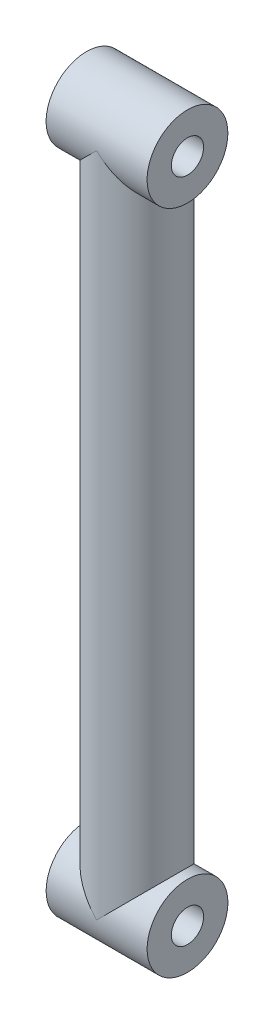
SolidWorks part; units mm, degrees
ref_plane "Front Plane" through (0, 0, 0) normal (0, 0, 1) x (1, 0, 0)
ref_plane "Top Plane" through (0, 0, 0) normal (0, 1, 0) x (1, 0, 0)
ref_plane "Right Plane" through (0, 0, 0) normal (1, 0, 0) x (0, 0, -1)
sketch "Sketch1" plane through (0, 0, 0) normal (0, 1, 0) x (1, 0, 0)
  circle A0 centre (0, 0) radius 10
  dimension "D1" = 20
extrude "Boss-Extrude1" add sketch "Sketch1" along normal blind 165
sketch "Sketch2" plane through (0, 0, 0) normal (1, 0, 0) x (0, 0, -1)
  line L0 (10, 165) -> (-10, 165) construction
  line L1 (-10, 82.5) -> (38.2537, 82.5) construction
  line L2 (-10, 165) -> (-10, 0) construction
  circle A0 centre (0, 165) radius 10
  circle A1 centre (0, 165) radius 4
  circle A2 centre (0, 0) radius 4
  circle A3 centre (0, 0) radius 10
  dimension "D1" = 20
  dimension "D2" = 8
extrude "Boss-Extrude2" add sketch "Sketch2" along normal blind 12.5 and the other way blind 12.5
extrude "Cut-Extrude1" cut sketch "Sketch2<2>" against normal through all both and the other way through all contours A1 | A2 region at (0, 165, 0) region at (0, 0, 0)
sketch "Sketch2<2>" plane through (0, 0, 0) normal (1, 0, 0) x (0, 0, -1) same geometry as "Sketch2"
